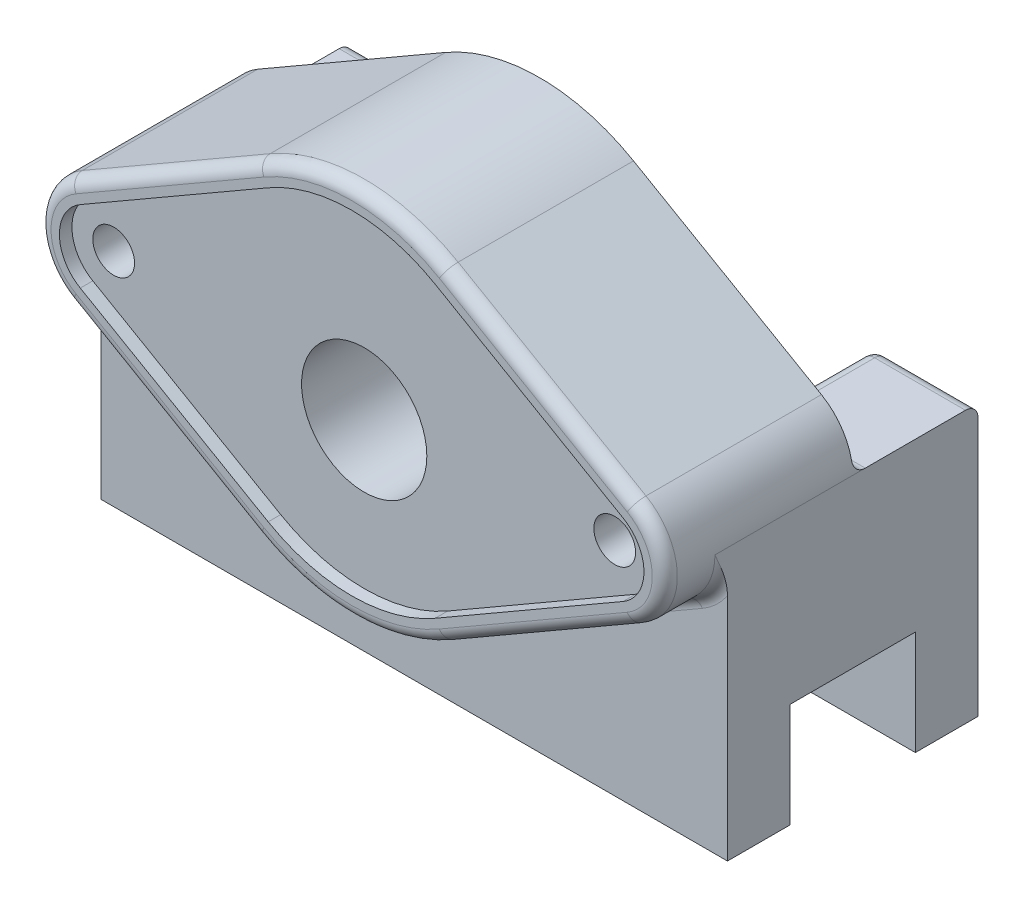
SolidWorks part; units mm, degrees
ref_plane "Front Plane" through (0, 0, 0) normal (0, 0, 1) x (1, 0, 0)
ref_plane "Top Plane" through (0, 0, 0) normal (0, 1, 0) x (1, 0, 0)
ref_plane "Right Plane" through (0, 0, 0) normal (1, 0, 0) x (0, 0, -1)
sketch "Sketch1" plane through (0, 0, 0) normal (0, 0, 1) x (1, 0, 0)
  line L0 (67.5, 52.0096) -> (22.5, 26.0289)
  line L1 (75, 65) -> (-75, 65)
  line L2 (75, 65) -> (75, 0)
  line L3 (75, 0) -> (-75, 0)
  line L4 (-75, 65) -> (-75, 0)
  line L5 (-22.5, 26.0289) -> (-67.5, 52.0096)
  line L6 (-67.5, 77.9904) -> (-22.5, 103.9711)
  line L7 (22.5, 103.9711) -> (67.5, 77.9904)
  arc A0 (22.5, 26.0289) -> (-22.5, 26.0289) centre (0, 65) cw
  arc A1 (67.5, 52.0096) -> (67.5, 77.9904) centre (60, 65) ccw
  arc A2 (-67.5, 52.0096) -> (-67.5, 77.9904) centre (-60, 65) cw
  arc A3 (-22.5, 103.9711) -> (22.5, 103.9711) centre (0, 65) cw
  point P4 (0, 0)
  point P15 (0, 20)
  point P16 (75, 65)
  point P19 (-75, 65)
  dimension "D3" = 45
  dimension "D4" = 15
  dimension "D5" = 15
  dimension "D6" = 45
  dimension "D1" = 150
  dimension "D2" = 65
extrude "Boss-Extrude1" add sketch "Sketch1" against normal blind 60 contours L2 L3 L4 L1
extrude "Boss-Extrude2" add sketch "Sketch1<3>" against normal blind 30 contours A3 L6 A2 L1 A1 L7 region at (0, 82.0779, 0)
sketch "Sketch1<3>" plane through (0, 0, 0) normal (0, 0, 1) x (1, 0, 0) same geometry as "Sketch1"
extrude "Boss-Extrude3" add sketch "Sketch1<4>" along normal blind 15 contours A3 L6 A2 L1 A1 L7 | A2 L5 A0 L0 A1 L1 region at (0, 47.9221, 0) region at (0, 82.0779, 0)
sketch "Sketch1<4>" plane through (0, 0, 0) normal (0, 0, 1) x (1, 0, 0) same geometry as "Sketch1"
sketch "Sketch2" plane through (0, 0, 0) normal (1, 0, 0) x (0, 0, -1)
  line L0 (60, 0) -> (0, 0) construction
  line L1 (45, 25) -> (15, 25)
  line L2 (45, 25) -> (45, 0)
  line L3 (45, 0) -> (15, 0)
  line L4 (15, 25) -> (15, 0)
  point P4 (30, 0)
  point P7 (30, 0)
  dimension "D1" = 30
  dimension "D2" = 25
extrude "Cut-Extrude1" cut sketch "Sketch2" against normal through all both and the other way through all
sketch "Sketch3" plane through (0, 0, 15) normal (0, 0, 1) x (1, 0, 0)
  line L13 (65, 73.6603) -> (20, 99.641)
  line L14 (20, 30.359) -> (65, 56.3397)
  line L15 (-65, 56.3397) -> (-20, 30.359)
  line L16 (-20, 99.641) -> (-65, 73.6603)
  line L17 (65, 73.6603) -> (20, 99.641)
  line L18 (20, 30.359) -> (65, 56.3397)
  line L19 (-65, 56.3397) -> (-20, 30.359)
  line L20 (-20, 99.641) -> (-65, 73.6603)
  arc A12 (20, 99.641) -> (-20, 99.641) centre (0, 65) ccw
  arc A13 (65, 56.3397) -> (65, 73.6603) centre (60, 65) ccw
  arc A14 (-20, 30.359) -> (20, 30.359) centre (0, 65) ccw
  arc A15 (-65, 73.6603) -> (-65, 56.3397) centre (-60, 65) ccw
  arc A16 (20, 99.641) -> (-20, 99.641) centre (0, 65) ccw
  arc A17 (65, 56.3397) -> (65, 73.6603) centre (60, 65) ccw
  arc A18 (-20, 30.359) -> (20, 30.359) centre (0, 65) ccw
  arc A19 (-65, 73.6603) -> (-65, 56.3397) centre (-60, 65) ccw
  dimension "D1" = 5
extrude "Cut-Extrude2" cut sketch "Sketch3" against normal blind 3
sketch "Sketch4" plane through (0, 0, 12) normal (0, 0, 1) x (1, 0, 0)
  circle A0 centre (0, 60) radius 15
  arc A2 (-15, 60) -> (15, 60) centre (0, 60) ccw construction
extrude "Cut-Extrude3" cut sketch "Sketch4" against normal through all
sketch "Sketch5" plane through (0, 0, 12) normal (0, 0, 1) x (1, 0, 0)
  arc A0 (-65, 73.6603) -> (-65, 56.3397) centre (-60, 65) ccw construction
  point P0 (-60, 65)
hole_wizard "Hole1" positions "Sketch6" profile "Sketch7" legacy
sketch "Sketch6" plane through (0, 0, 12) normal (0, 0, 1) x (1, 0, 0)
  point P0 (-60, 65)
sketch "Sketch7" plane through (-60, 65, 12) normal (1, 0, 0) x (0, -1, 0)
  line L0 (0, 0) -> (0, 30)
  line L1 (0, 30) -> (5, 30)
  line L2 (5, 30) -> (5, 0)
  line L3 (5, 0) -> (0, 0)
  line L4 (0, 110) -> (0, -10) construction
  dimension "Diameter" = 10
  dimension "Depth" = 30
mirror "Mirror1" about plane through (0, 0, 0) normal (1, 0, 0) of "Hole1"
sketch "Sketch8" plane through (0, 0, -60) normal (0, 0, -1) x (-1, 0, 0)
  circle A0 centre (0, 85) radius 55
  dimension "D1" = 110
  dimension "D2" = 85
extrude "Cut-Extrude4" cut sketch "Sketch8" against normal up to surface (30 mm away) up to face at (0, 80.2452, -30)
fillet "Fillet1" radius 3 21 edges at (72.9904, 57.5, 0) (45, 39.0192, 0) (-72.9904, 57.5, 0) (-45, 39.0192, 0) (-45, 90.9808, 15) (-75, 65, 15) (-45, 39.0192, 15) (0, 20, 15) (45, 39.0192, 15) (75, 65, 15) (45, 90.9808, 15) (-63.1174, 65, -30) (63.1174, 65, -30) (0, 30, -30) (0, 20, 0) (0, 110, 15) (-51.2348, 65, -45) (-63.1174, 65, -60) (0, 30, -60) (63.1174, 65, -60) (51.2348, 65, -45)
